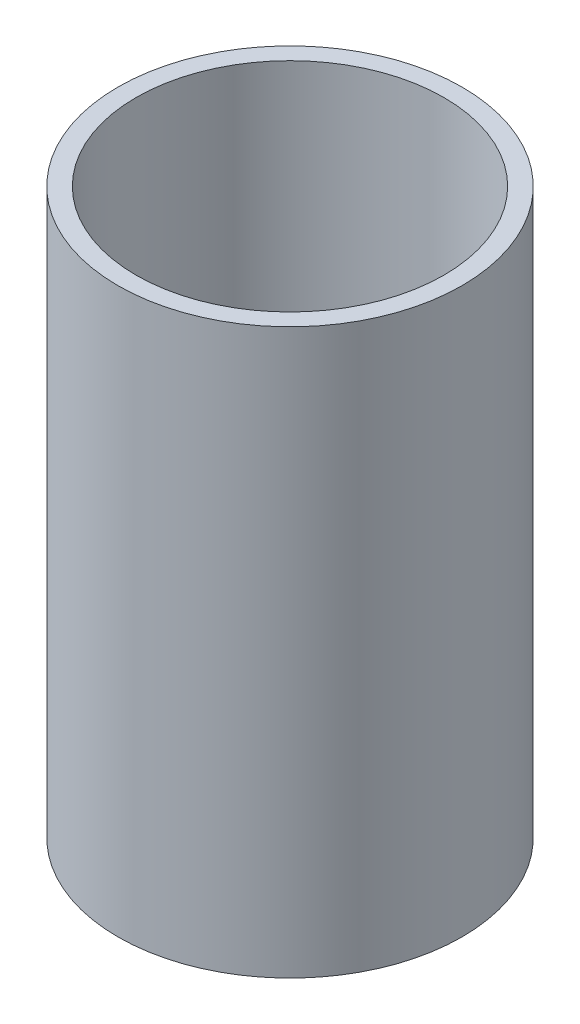
SolidWorks part; units mm, degrees
ref_plane "Front Plane" through (0, 0, 0) normal (0, 0, 1) x (1, 0, 0)
ref_plane "Top Plane" through (0, 0, 0) normal (0, 1, 0) x (1, 0, 0)
ref_plane "Right Plane" through (0, 0, 0) normal (1, 0, 0) x (0, 0, -1)
sketch "Sketch1" plane through (0, 0, 0) normal (0, 1, 0) x (1, 0, 0)
  circle A0 centre (0, 0) radius 30.1625
  circle A1 centre (0, 0) radius 26.9875
extrude "Boss-Extrude1" add sketch "Sketch1" along normal blind 98.9
